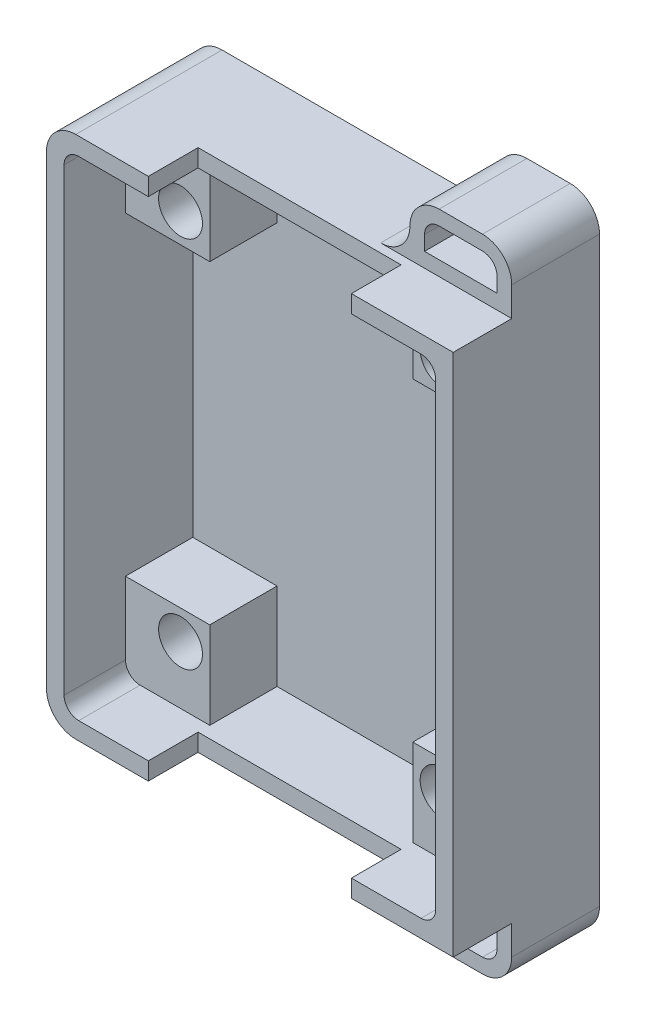
SolidWorks part; units mm, degrees
ref_plane "Ebene vorne" through (0, 0, 0) normal (0, 0, 1) x (1, 0, 0)
ref_plane "Ebene oben" through (0, 0, 0) normal (0, 1, 0) x (1, 0, 0)
ref_plane "Ebene rechts" through (0, 0, 0) normal (1, 0, 0) x (0, 0, -1)
ref_plane "Ebene1"
sketch "Skizze1" plane through (0, 0, 0) normal (0, 0, 1) x (1, 0, 0)
  line L0 (0, -35.8) -> (27.8, -35.8)
  line L1 (27.8, -35.8) -> (27.8, 0)
  line L2 (27.8, 0) -> (0, 0)
  line L3 (0, 0) -> (0, -35.8)
  dimension "D1" = 27.8
  dimension "D2" = 35.8
extrude "Extrusion1" add sketch "Skizze1" along normal blind 12
sketch "Skizze2" plane through (0, 0, 12) normal (0, 0, 1) x (1, 0, 0)
  line L0 (1.2, -34.6) -> (26.6, -34.6)
  line L1 (26.6, -34.6) -> (26.6, -1.2)
  line L2 (26.6, -1.2) -> (1.2, -1.2)
  line L3 (1.2, -1.2) -> (1.2, -34.6)
  line L4 (0, 0) -> (0, -35.8) construction
  line L5 (27.8, 0) -> (0, 0) construction
  line L6 (27.8, -35.8) -> (27.8, 0) construction
  line L7 (0, -35.8) -> (27.8, -35.8) construction
  dimension "D1" = 1.2
  dimension "D2" = 1.2
  dimension "D3" = 1.2
  dimension "D4" = 1.2
extrude "Extrusion2" cut sketch "Skizze2" against normal blind 10.8
ref_plane "Ebene2"
sketch "Skizze3" plane through (0, 0, 1.2) normal (0, 0, 1) x (1, 0, 0)
  line L0 (1.2, -1.2) -> (1.2, -34.6) construction
  line L1 (26.6, -34.6) -> (26.6, -1.2) construction
  line L2 (26.6, -1.2) -> (1.2, -1.2) construction
  line L3 (1.2, -34.6) -> (26.6, -34.6) construction
  circle A0 centre (22.84, -30.65) radius 1.5
  circle A1 centre (4.96, -30.65) radius 1.5
  circle A2 centre (22.84, -5.15) radius 1.5
  circle A3 centre (4.96, -5.15) radius 1.5
  dimension "D2" = 3
  dimension "D3" = 3
  dimension "D4" = 3
  dimension "D5" = 3
  dimension "D1" = 25.5
  dimension "D6" = 25.4
  dimension "D7" = 33.4
extrude "Extrusion3" cut sketch "Skizze3" against normal blind 10.8 contours A0 | A1 | A2 | A3
ref_plane "Ebene3"
sketch "Skizze4" plane through (0, 0, 1.2) normal (0, 0, 1) x (1, 0, 0)
  line L0 (1.2, -7.15) -> (6.96, -7.15)
  line L1 (6.96, -7.15) -> (6.96, -1.2)
  line L2 (6.96, -1.2) -> (1.2, -1.2)
  line L3 (1.2, -1.2) -> (1.2, -7.15)
  line L4 (26.6, -1.2) -> (20.84, -1.2)
  line L5 (20.84, -1.2) -> (20.84, -7.15)
  line L6 (20.84, -7.15) -> (26.6, -7.15)
  line L7 (26.6, -7.15) -> (26.6, -1.2)
  line L8 (26.6, -28.65) -> (20.84, -28.65)
  line L9 (20.84, -28.65) -> (20.84, -34.6)
  line L10 (20.84, -34.6) -> (26.6, -34.6)
  line L11 (26.6, -34.6) -> (26.6, -28.65)
  line L12 (1.2, -34.6) -> (6.96, -34.6)
  line L13 (6.96, -34.6) -> (6.96, -28.65)
  line L14 (6.96, -28.65) -> (1.2, -28.65)
  line L15 (1.2, -28.65) -> (1.2, -34.6)
  circle A0 centre (4.96, -5.15) radius 1.5
  circle A1 centre (22.84, -5.15) radius 1.5
  circle A2 centre (22.84, -30.65) radius 1.5
  circle A3 centre (4.96, -30.65) radius 1.5
extrude "Extrusion4" add sketch "Skizze4" along normal blind 6.6 contours L2 L3 L0 L1 A0 | L6 L7 L4 L5 A1 | L10 L11 L8 L9 A2 | L14 L15 L12 L13 A3
sketch "Skizze5" plane through (0, 0, 0) normal (0, 1, 0) x (-1, 0, 0)
  line L0 (-20.84, 8.6) -> (-6.96, 8.6)
  line L1 (-6.96, 8.6) -> (-6.96, 12)
  line L2 (-6.96, 12) -> (-20.84, 12)
  line L3 (-20.84, 12) -> (-20.84, 8.6)
extrude "Extrusion5" cut sketch "Skizze5" against normal through all
ref_plane "Ebene4"
sketch "Skizze6" plane through (0, 0, 1.2) normal (0, 0, 1) x (1, 0, 0)
  line L0 (26.6, -1.2) -> (1.2, -1.2)
  line L1 (1.2, -1.2) -> (1.2, -34.6)
  line L2 (1.2, -34.6) -> (20.84, -34.6)
  line L3 (20.84, -34.6) -> (26.6, -34.6)
  line L4 (26.6, -34.6) -> (26.6, -1.2)
extrude "Extrusion6" add sketch "Skizze6" along normal blind 2
sketch "Skizze7" plane through (0, 0, 0) normal (0, 0, -1) x (-1, 0, 0)
  line L0 (-27.8, -35.8) -> (0, -35.8)
  line L1 (0, -35.8) -> (0, 0)
  line L2 (0, 0) -> (-27.8, 0)
  line L3 (-27.8, 0) -> (-27.8, -35.8)
extrude "Extrusion7" cut sketch "Skizze7" against normal blind 2
sketch "Skizze8" plane through (0, -35.8, 0) normal (0, -1, 0) x (1, 0, 0)
  line L0 (27.8, 8) -> (20.84, 8)
  line L1 (20.84, 8) -> (20.84, 2)
  line L2 (20.84, 2) -> (27.8, 2)
  line L3 (27.8, 2) -> (27.8, 8)
extrude "Extrusion8" add sketch "Skizze8" along normal blind 4
sketch "Skizze9" plane through (0, 0, 2) normal (0, 0, -1) x (-1, 0, 0)
  line L0 (-26.8, -38.8) -> (-21.84, -38.8)
  line L1 (-21.84, -38.8) -> (-21.84, -36.8)
  line L2 (-21.84, -36.8) -> (-26.8, -36.8)
  line L3 (-26.8, -36.8) -> (-26.8, -38.8)
  line L4 (-20.84, -39.8) -> (-27.8, -39.8) construction
  line L5 (-20.84, -39.8) -> (-20.84, -35.8) construction
  line L6 (-27.8, 0) -> (-27.8, -39.8) construction
  dimension "D1" = 2
  dimension "D2" = 1
  dimension "D3" = 1
  dimension "D4" = 1
extrude "Extrusion9" cut sketch "Skizze9" against normal through all
sketch "Skizze10" plane through (0, 0, 2) normal (0, 0, -1) x (-1, 0, 0)
  line L0 (-20.84, 4) -> (-27.8, 4)
  line L1 (-27.8, 4) -> (-27.8, 0)
  line L2 (-27.8, 0) -> (-20.84, 0)
  line L3 (-20.84, 0) -> (-20.84, 4)
  line L4 (-21.84, 1) -> (-26.8, 1)
  line L5 (-26.8, 1) -> (-26.8, 3)
  line L6 (-26.8, 3) -> (-21.84, 3)
  line L7 (-21.84, 3) -> (-21.84, 1)
  line M12 (0, 0) -> (-27.8, 0)
  dimension "D1" = 4
  dimension "D2" = 1
  dimension "D3" = 2
extrude "Extrusion10" add sketch "Skizze10" against normal blind 6 contours L3 L0 L1 L6 L7 L4 L5 M12
fillet "Rundung1" radius 2 8 edges at (0, 0, 7) (0, -35.8, 7) (20.84, -39.8, 5) (27.8, -39.8, 5) (20.84, 4, 5) (27.8, 4, 5) (20.84, -35.8, 5) (20.84, 0, 5)
fillet "Rundung2" radius 1 4 edges at (26.6, -1.2, 9.9) (1.2, -1.2, 9.9) (26.6, -34.6, 9.9) (1.2, -34.6, 9.9)
fillet "Rundung3" radius 1 4 edges at (26.8, -38.8, 5) (21.84, -38.8, 5) (26.8, 3, 5) (21.84, 3, 5)
ref_plane "Ebene5"
sketch "Skizze11" plane through (0, 0, 7.8) normal (0, 0, 1) x (1, 0, 0)
  circle A0 centre (4.96, -5.15) radius 1.5
  circle A1 centre (22.84, -5.15) radius 1.5
  circle A2 centre (4.96, -30.65) radius 1.5
  circle A3 centre (22.84, -30.65) radius 1.5
extrude "Extrusion11" cut sketch "Skizze11" against normal blind 10 contours A0 | A1 | A2 | A3
